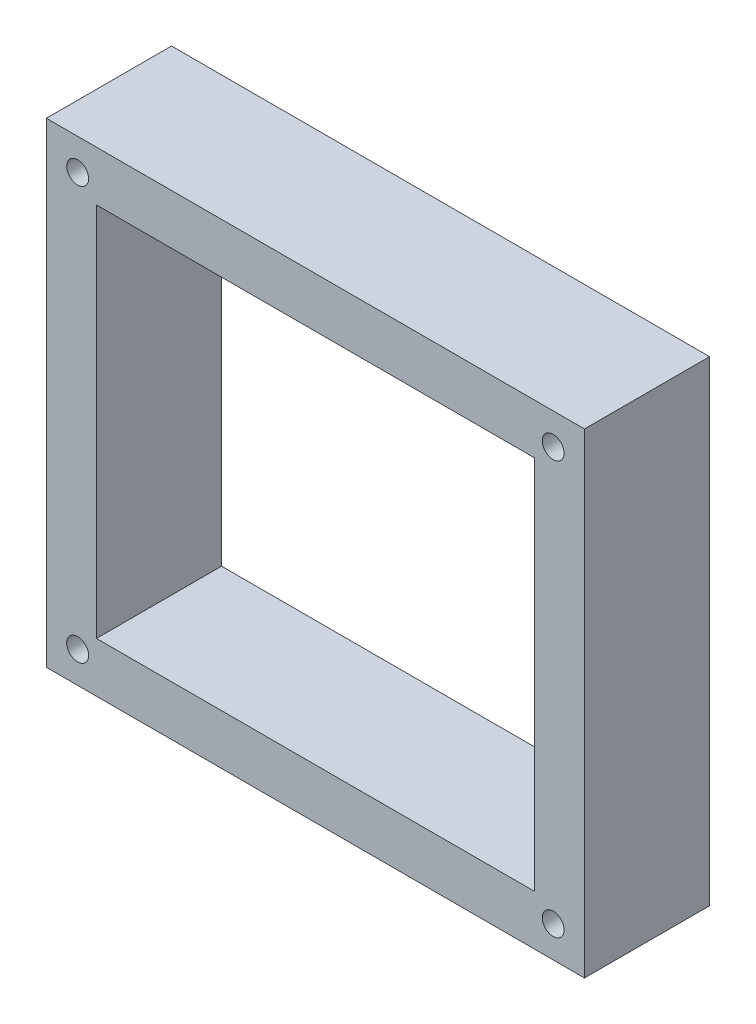
SolidWorks part; units mm, degrees
ref_plane "前视基准面" through (0, 0, 0) normal (0, 0, 1) x (1, 0, 0)
ref_plane "上视基准面" through (0, 0, 0) normal (0, 1, 0) x (1, 0, 0)
ref_plane "右视基准面" through (0, 0, 0) normal (1, 0, 0) x (0, 0, -1)
sketch "草图1" plane through (0, 0, 0) normal (0, 0, 1) x (1, 0, 0)
  line L0 (-43, 38) -> (-43, -38)
  line L1 (-35, 30) -> (35, 30)
  line L2 (-35, 30) -> (-35, -30)
  line L3 (-35, -30) -> (35, -30)
  line L4 (35, 30) -> (35, -30)
  line L5 (-35, 30) -> (35, -30) construction
  line L6 (-35, -30) -> (35, 30) construction
  line L7 (-43, -38) -> (43, -38)
  line L8 (43, 38) -> (43, -38)
  line L9 (-43, 38) -> (43, 38)
  line L10 (35, 30) -> (43, 38) construction
  line L11 (35, -30) -> (43, -38) construction
  line L12 (-35, -30) -> (-43, -38) construction
  line L13 (-35, 30) -> (-43, 38) construction
  line L14 (-43, 38) -> (-43, 33) construction
  line L15 (-43, 33) -> (-38, 33) construction
  line L16 (-43, 0) -> (43, 0) construction
  line L17 (0, -30) -> (0, 30) construction
  circle A0 centre (-38, 33) radius 1.75
  circle A1 centre (38, 33) radius 1.75
  circle A2 centre (38, -33) radius 1.75
  circle A3 centre (-38, -33) radius 1.75
  point P0 (0, 0)
  dimension "D1" = 8
extrude "凸台-拉伸1" add sketch "草图1" along normal blind 20
